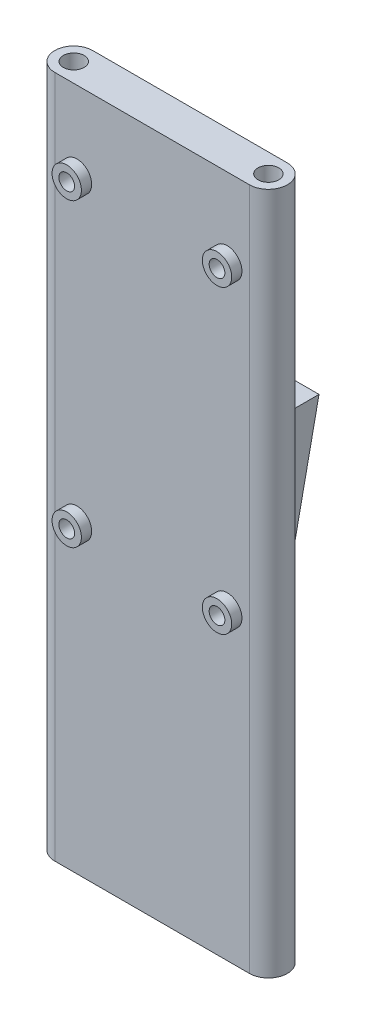
SolidWorks part; units mm, degrees
ref_plane "Front Plane" through (0, 0, 0) normal (0, 0, 1) x (1, 0, 0)
ref_plane "Top Plane" through (0, 0, 0) normal (0, 1, 0) x (1, 0, 0)
ref_plane "Right Plane" through (0, 0, 0) normal (1, 0, 0) x (0, 0, -1)
sketch "Sketch1" plane through (0, 0, 0) normal (0, 1, 0) x (1, 0, 0)
  line L0 (-28.5, 0) -> (28.5, 0) construction
  line L1 (-28.5, 0) -> (28.5, 0) construction
  line L2 (-28.5, 5.55) -> (28.5, 5.55)
  line L3 (-28.5, -5.55) -> (28.5, -5.55)
  circle A0 centre (-28.5, 0) radius 3.05
  circle A1 centre (28.5, 0) radius 3.05
  arc A2 (-28.5, 5.55) -> (-28.5, -5.55) centre (-28.5, 0) ccw
  arc A3 (28.5, -5.55) -> (28.5, 5.55) centre (28.5, 0) ccw
  point P4 (0, 0)
  dimension "D1" = 6.1
  dimension "D2" = 2.5
  dimension "D3" = 57
extrude "Boss-Extrude1" add sketch "Sketch1" along normal mid plane 200
sketch "Sketch2" plane through (0, 0, 0) normal (1, 0, 0) x (0, 0, -1)
  line L0 (5.55, 36.6649) -> (5.55, -0.5321)
  line L1 (5.55, 100) -> (5.55, -100) construction
  line L2 (5.55, -0.5321) -> (7.05, -0.5321)
  line L3 (7.05, -0.5321) -> (14.8208, 36.6649)
  line L4 (14.8208, 36.6649) -> (5.55, 36.6649)
  dimension "D1" = 11.8
  dimension "D2" = 38
  dimension "D3" = 1.5
extrude "Boss-Extrude2" add sketch "Sketch2" along normal up to vertex (28.5 mm away) and the other way up to vertex (28.5 mm away) up to point (28.5, 100, -5.55) other way up to point (-28.5, 100, -5.55)
sketch "Sketch3" plane through (0, -1.4335, -6.8617) normal (0, -0.2045, -0.9789) x (-1, 0, 0)
  line L0 (-14, 33.9209) -> (14, 5.9209) construction
  line L1 (0, 11.204) -> (0, -11.204) construction
  line L3 (-28.5, 0.9209) -> (-28.5, 38.9209) construction
  circle A0 centre (-14, 33.9209) radius 1.5
  circle A1 centre (-14, 5.9209) radius 1.5
  circle A2 centre (14, 33.9209) radius 1.5
  circle A3 centre (14, 5.9209) radius 1.5
  circle A4 centre (-14, 33.9209) radius 2.5
  circle A5 centre (14, 33.9209) radius 2.5
  circle A6 centre (14, 5.9209) radius 2.5
  circle A7 centre (-14, 5.9209) radius 2.5
  point P8 (0, 19.9209)
  point P13 (-28.5, 19.9209)
  dimension "D1" = 3
  dimension "D2" = 28
  dimension "D3" = 28
  dimension "D4" = 1
extrude "Boss-Extrude3" add sketch "Sketch3" along normal blind 1.5
chamfer "Chamfer1" distance 0.5 angle 45 4 edges at (14, 6.5027, -10.052) (-14, 6.5027, -10.052) (-14, 33.911, -15.7779) (14, 33.911, -15.7779)
sketch "Sketch4" plane through (0, 0, 5.55) normal (0, 0, 1) x (1, 0, 0)
  line L0 (0, -11.6741) -> (0, 11.6741) construction
  line L1 (-26, 100) -> (26, 100) construction
  line L2 (-26, 100) -> (-26, -15) construction
  line L3 (-26, -15) -> (26, -15) construction
  line L4 (26, 100) -> (26, -15) construction
  line L5 (-28.5, 100) -> (28.5, 100) construction
  line L6 (-22, 77) -> (22, 77) construction
  line L7 (-22, -11) -> (22, -11) construction
  circle A0 centre (-22, 77) radius 2.3
  circle A1 centre (22, 77) radius 2.3
  circle A2 centre (-22, -11) radius 2.3
  circle A3 centre (22, -11) radius 2.3
  circle A4 centre (-22, 77) radius 4.3
  circle A5 centre (22, 77) radius 4.3
  circle A6 centre (-22, -11) radius 4.3
  circle A7 centre (22, -11) radius 4.3
  point P4 (0, 100)
  point P12 (0, 77)
  point P16 (0, -11)
  dimension "D7" = 4.6
  dimension "D1" = 52
  dimension "D2" = 115
  dimension "D3" = 23
  dimension "D4" = 4
  dimension "D5" = 4
  dimension "D6" = 4
  dimension "D8" = 2
extrude "Boss-Extrude4" add sketch "Sketch4" along normal blind 3
extrude "Cut-Extrude1" cut sketch "Sketch4<2>" against normal blind 3 contours A1 | A0 | A3 | A2 region at (-22, 77, 5.55) region at (22, 77, 5.55) region at (-22, -11, 5.55) region at (22, -11, 5.55)
sketch "Sketch4<2>" plane through (0, 0, 5.55) normal (0, 0, 1) x (1, 0, 0) same geometry as "Sketch4"
